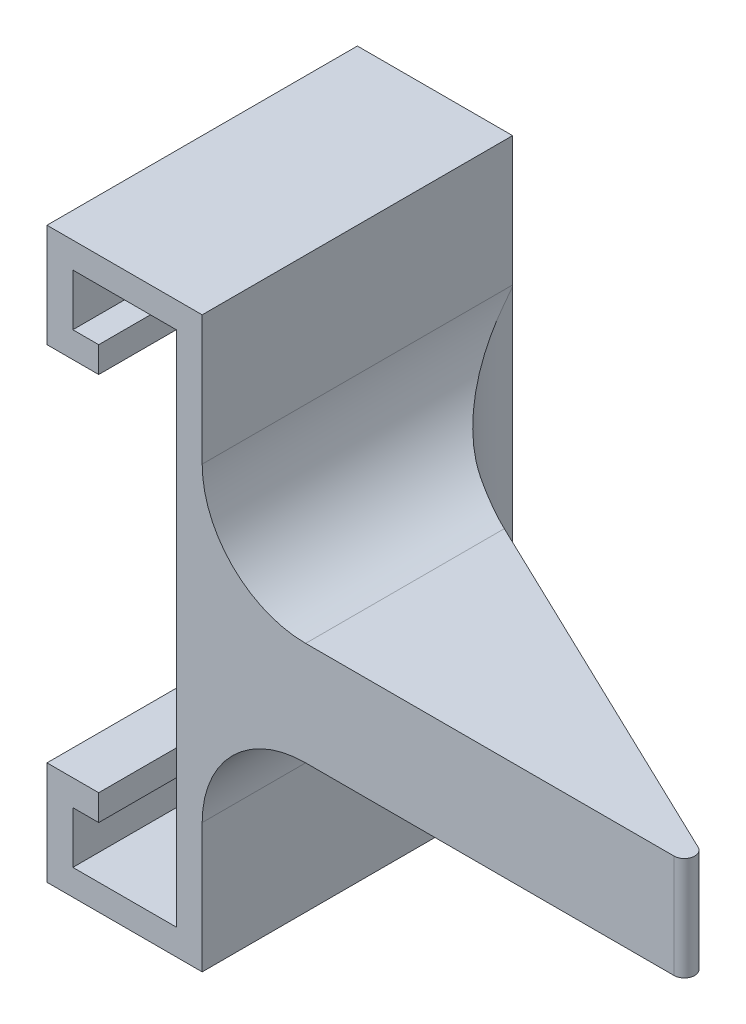
SolidWorks part; units mm, degrees
material "ABS"
ref_plane "Front Plane" through (0, 0, 0) normal (0, 0, 1) x (1, 0, 0)
ref_plane "Top Plane" through (0, 0, 0) normal (0, 1, 0) x (1, 0, 0)
ref_plane "Right Plane" through (0, 0, 0) normal (1, 0, 0) x (0, 0, -1)
sketch "Sketch2" plane through (0, 0, 0) normal (0, 0, 1) x (1, 0, 0)
  line L0 (0, 0) -> (-5, 0)
  line L1 (-5, 0) -> (-5, 10)
  line L2 (-5, 10) -> (10, 10)
  line L3 (10, 10) -> (10, -45)
  line L4 (10, -45) -> (-5, -45)
  line L5 (-5, -45) -> (-5, -35)
  line L6 (-5, -35) -> (0, -35)
  line L7 (0, -35) -> (0, -37.5)
  line L8 (0, -37.5) -> (-2.5, -37.5)
  line L9 (-2.5, -37.5) -> (-2.5, -42.5)
  line L10 (-2.5, -42.5) -> (7.5, -42.5)
  line L11 (7.5, -42.5) -> (7.5, 7.5)
  line L12 (7.5, 7.5) -> (-2.5, 7.5)
  line L13 (-2.5, 7.5) -> (-2.5, 2.5)
  line L14 (-2.5, 2.5) -> (0, 2.5)
  line L15 (0, 2.5) -> (0, 0)
  point P3 (-2.5, -40)
  point P20 (0, 1.25)
  dimension "D1" = 10
  dimension "D2" = 10
  dimension "D3" = 2.5
  dimension "D4" = 2.5
  dimension "D5" = 2.5
  dimension "D6" = 2.5
  dimension "D7" = 2.5
  dimension "D8" = 2.5
  dimension "D9" = 2.5
  dimension "D10" = 50
  dimension "D11" = 7.5
  dimension "D12" = 10
extrude "Boss-Extrude1" add sketch "Sketch2" along normal blind 30
ref_plane "Plane1" through (0, -17.5, 0) normal (0, -1, 0) x (-1, 0, 0)
sketch "Sketch3" plane through (0, -17.5, 0) normal (0, -1, 0) x (-1, 0, 0)
  line L0 (-10, -6) -> (-60, -30)
  line L1 (-60, -30) -> (-10, -30)
  line L2 (-10, -30) -> (-10, 0) construction
  line L3 (-10, -30) -> (-10, -6)
  line L4 (5, -30) -> (-10, -30) construction
  dimension "D1" = 50
  dimension "D2" = 24
extrude "Boss-Extrude2" add sketch "Sketch3" along normal blind 5 and the other way blind 5
fillet "Fillet1" radius 10 3 edges at (10, -12.5, 18) (10, -22.5, 18) (10, -17.5, 6)
fillet "Fillet2" radius 1 1 edges at (60, -17.5, 30)
